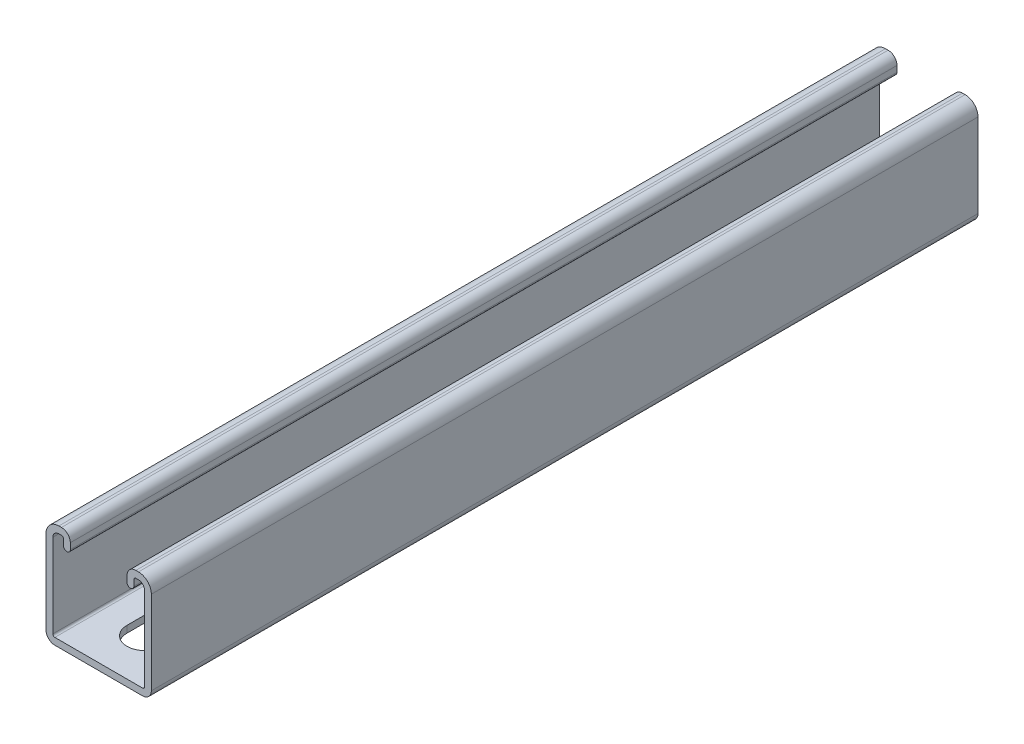
SolidWorks part; units mm, degrees
ref_plane "Front Plane" through (0, 0, 0) normal (0, 0, 1) x (1, 0, 0)
ref_plane "Top Plane" through (0, 0, 0) normal (0, 1, 0) x (1, 0, 0)
ref_plane "Right Plane" through (0, 0, 0) normal (1, 0, 0) x (0, 0, -1)
ref_plane "Plane1" through (0, 0, 3048) normal (0, 0, 1) x (1, 0, 0)
sketch "Sketch1" plane through (0, 0, 0) normal (0, 0, 1) x (1, 0, 0)
  line L0 (-20.6377, 0) -> (-17.9706, 0) construction
  line L1 (20.6377, 0) -> (17.9706, 0) construction
  line L2 (17.1769, -17.9704) -> (-17.1769, -17.9704)
  line L3 (-17.9706, -17.1766) -> (-17.9706, 15.5891)
  line L4 (-15.5894, 17.9704) -> (-14.5734, 17.9704)
  line L5 (-13.7797, 17.1766) -> (-13.7797, 14.8335)
  line L6 (-11.1127, 14.8335) -> (-11.1127, 17.1766)
  line L7 (-14.5734, 20.6374) -> (-15.5894, 20.6374)
  line L8 (-20.6377, 15.5891) -> (-20.6377, -17.1766)
  line L9 (-17.1769, -20.6374) -> (17.1769, -20.6374)
  line L10 (20.6377, 15.5891) -> (20.6377, -17.1766)
  line L11 (14.5734, 20.6374) -> (15.5894, 20.6374)
  line L12 (11.1127, 14.8335) -> (11.1127, 17.1766)
  line L13 (13.7797, 17.1766) -> (13.7797, 14.8335)
  line L14 (0, -17.9704) -> (0, -20.6374) construction
  line L15 (15.5894, 17.9704) -> (14.5734, 17.9704)
  line L16 (17.9706, -17.1766) -> (17.9706, 15.5891)
  arc A0 (-17.1769, -20.6374) -> (-20.6377, -17.1766) centre (-17.1769, -17.1766) cw
  arc A1 (-17.1769, -17.9704) -> (-17.9706, -17.1766) centre (-17.1769, -17.1766) cw
  arc A2 (-17.9706, 15.5891) -> (-15.5894, 17.9704) centre (-15.5894, 15.5891) cw
  arc A3 (-20.6377, 15.5891) -> (-15.5894, 20.6374) centre (-15.5894, 15.5891) cw
  arc A4 (-14.5734, 17.9704) -> (-13.7797, 17.1766) centre (-14.5734, 17.1766) cw
  arc A5 (-14.5734, 20.6374) -> (-11.1127, 17.1766) centre (-14.5734, 17.1766) cw
  arc A6 (-13.7797, 14.8335) -> (-11.1127, 14.8335) centre (-12.4462, 14.8335) ccw
  arc A7 (13.7797, 14.8335) -> (11.1127, 14.8335) centre (12.4462, 14.8335) cw
  arc A8 (14.5734, 20.6374) -> (11.1127, 17.1766) centre (14.5734, 17.1766) ccw
  arc A9 (14.5734, 17.9704) -> (13.7797, 17.1766) centre (14.5734, 17.1766) ccw
  arc A10 (20.6377, 15.5891) -> (15.5894, 20.6374) centre (15.5894, 15.5891) ccw
  arc A11 (17.9706, 15.5891) -> (15.5894, 17.9704) centre (15.5894, 15.5891) ccw
  arc A12 (17.1769, -17.9704) -> (17.9706, -17.1766) centre (17.1769, -17.1766) ccw
  arc A13 (17.1769, -20.6374) -> (20.6377, -17.1766) centre (17.1769, -17.1766) ccw
  dimension "D4" = 3.4608
  dimension "D5" = 5.0483
  dimension "D7" = 3.4608
  dimension "D1" = 34.3538
  dimension "D2" = 41.2748
  dimension "D3" = 2.667
  dimension "D6" = 1.016
  dimension "D8" = 2.3432
extrude "Primary Extrusion" add sketch "Sketch1" against normal blind 323.85
sketch "Sketch58" plane through (0, -20.6374, 0) normal (0, 1, 0) x (-1, 0, 0)
  line L0 (7.1438, -32.5438) -> (7.1438, -18.2562)
  line L1 (-7.1438, -18.2563) -> (-7.1438, -32.5438)
  line L2 (0, 22.7012) -> (0, -22.7012) construction
  line L3 (-7.1438, -25.4) -> (7.1438, -25.4) construction
  line L4 (17.1769, 0) -> (-17.1769, 0) construction
  arc A0 (7.1438, -32.5438) -> (-7.1438, -32.5438) centre (0, -32.5438) cw
  arc A1 (-7.1438, -18.2563) -> (7.1438, -18.2562) centre (0, -18.2563) cw
  dimension "D1" = 14.2875
  dimension "D2" = 14.2875
  dimension "D3" = 25.4
extrude "Slot Cut" cut sketch "Sketch58" along normal up to next contours L0 A1 L1 A0
pattern_linear "LPattern1" count 7 spacing 50.8 along (0, 0, -1) of "Slot Cut"
